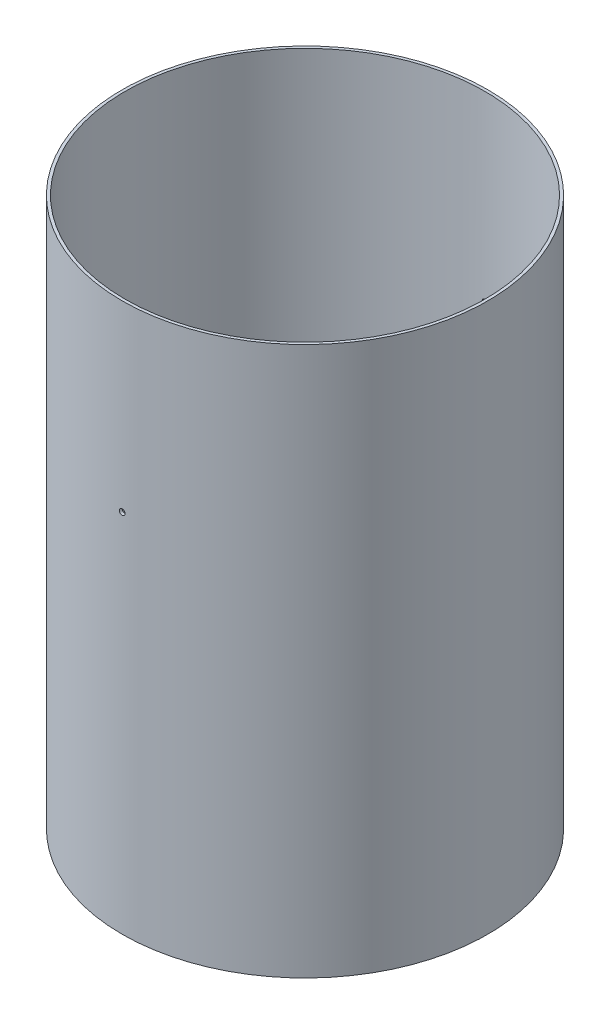
SolidWorks part; units mm, degrees
ref_plane "Front Plane" through (0, 0, 0) normal (0, 0, 1) x (1, 0, 0)
ref_plane "Top Plane" through (0, 0, 0) normal (0, 1, 0) x (1, 0, 0)
ref_plane "Right Plane" through (0, 0, 0) normal (1, 0, 0) x (0, 0, -1)
sketch "Sketch1" plane through (0, 0, 0) normal (0, 1, 0) x (1, 0, 0)
  circle A0 centre (0, 0) radius 101.6
  circle A1 centre (0, 0) radius 100.0125
  dimension "D1" = 203.2
  dimension "D2" = 200.025
extrude "Boss-Extrude1" add sketch "Sketch1" along normal blind 304.8
ref_plane "Plane1" through (0, 0, 101.6) normal (0, 0, 1) x (1, 0, 0)
sketch "Sketch10" plane through (0, 0, 101.6) normal (0, 0, 1) x (1, 0, 0)
  line L0 (101.6, 304.8) -> (-101.6, 304.8) construction
  circle A0 centre (0, 203.2) radius 1.5875
  dimension "D1" = 3.175
  dimension "D2" = 101.6
extrude "Cut-Extrude1" cut sketch "Sketch10" against normal through all both and the other way through all
